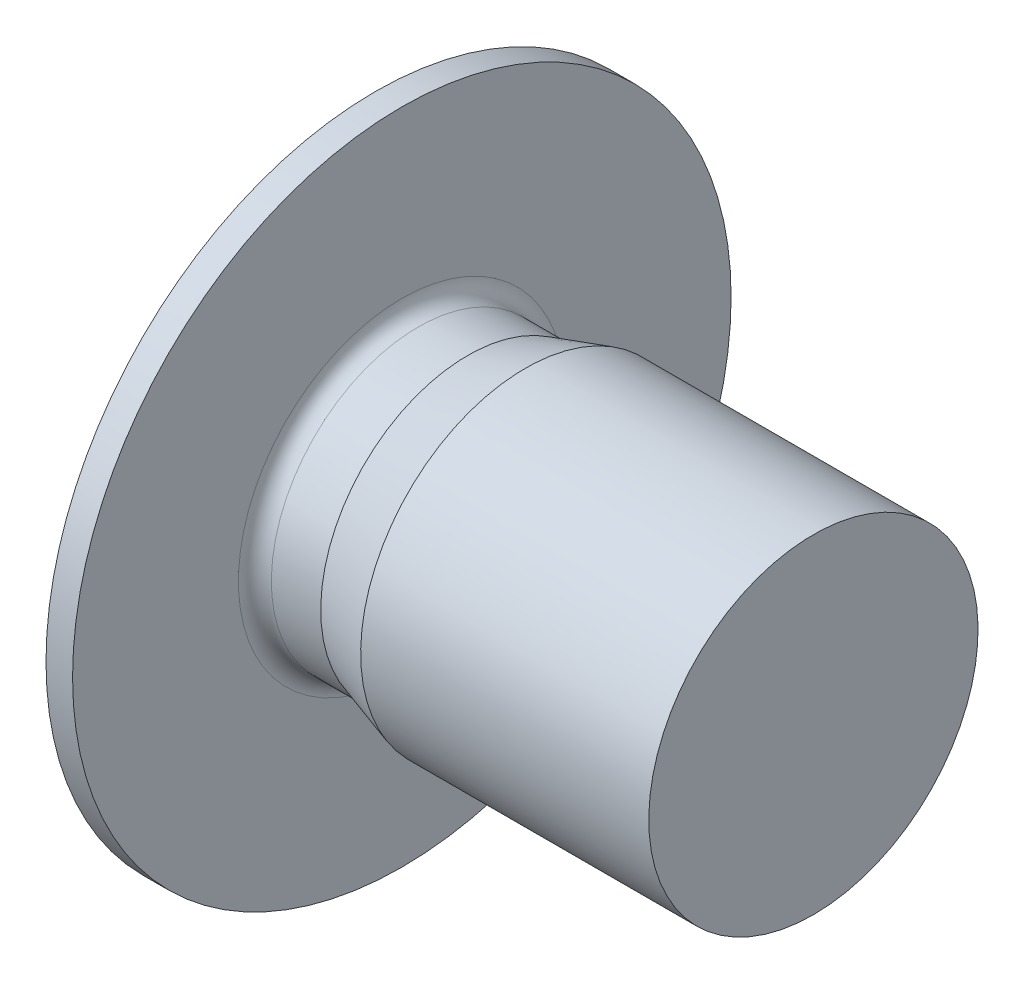
SolidWorks part; units mm, degrees
material "SUS304相当"
ref_plane "Front Plane" through (0, 0, 0) normal (0, 0, 1) x (1, 0, 0)
ref_plane "Top Plane" through (0, 0, 0) normal (0, 1, 0) x (1, 0, 0)
ref_plane "Right Plane" through (0, 0, 0) normal (1, 0, 0) x (0, 0, -1)
sketch "Sketch1" plane through (0, 0, 0) normal (0, 0, 1) x (1, 0, 0)
  line L0 (-0.9, 0) -> (5, 0) construction
  line L1 (-0.9, 0) -> (-0.9, 3)
  line L2 (-0.3226, 4) -> (0, 4)
  line L3 (0, 4) -> (0, 1.785)
  line L4 (1.5, 2) -> (5, 2)
  line L5 (5, 2) -> (5, 0)
  line L6 (5, 0) -> (-0.9, 0)
  line L7 (1.5, 2) -> (0.8, 1.785)
  line L8 (0.8, 1.785) -> (0, 1.785)
  line L9 (-0.3226, 4) -> (-0.9, 3)
  line L10 (-0.9, 0) -> (5, 0) construction
  dimension "A" = 8
  dimension "M" = 4
  dimension "L" = 5
  dimension "MSM_1" = 6
  dimension "E_s" = 1.5
  dimension "E" = 0.9
  dimension "FIX_1" = 30
  dimension "MSM_2" = 3.57
  dimension "MSM_3" = 0.7
revolve "Revolve1" add sketch "Sketch1" angle 360 about L0
cosmetic thread "Thread1" parameters "ATL_1"=3.5, "ATD"=3.242
fillet "Fillet1" radius 0.2 1 edges at (0, -1.785, 0)
sketch "Sketch2" plane through (-0.9, 0, 0) normal (-1, 0, 0) x (0, 0, 1)
  line L1 (0, 1.1547) -> (-1, 0.5774)
  line L2 (-1, 0.5774) -> (-1, -0.5774)
  line L3 (-1, -0.5774) -> (0, -1.1547)
  line L4 (0, -1.1547) -> (1, -0.5774)
  line L5 (1, -0.5774) -> (1, 0.5774)
  line L6 (1, 0.5774) -> (0, 1.1547)
  circle A0 centre (0, 0) radius 1 construction
  dimension "B" = 2
extrude "Cut-Extrude1" cut sketch "Sketch2" against normal blind 2.5
sketch "Sketch3" plane through (0, 0, 0) normal (0, 0, 1) x (1, 0, 0)
  line L0 (1.6, 0) -> (2.2009, 0) construction
  line L1 (1.6, 0) -> (1.6, 1)
  line L2 (1.6, 1) -> (2.2009, 0)
  line L3 (2.2009, 0) -> (1.6, 0)
  line L5 (1.6, 0.5774) -> (1.6, -0.5774) construction
  dimension "FIX_3" = 59
  dimension "B" = 2
revolve "Cut-Revolve1" cut sketch "Sketch3" angle 360 about L0
equation "\"ATL_1@Thread1\" = \"L@Sketch1\" - \"E_s@Sketch1\""
